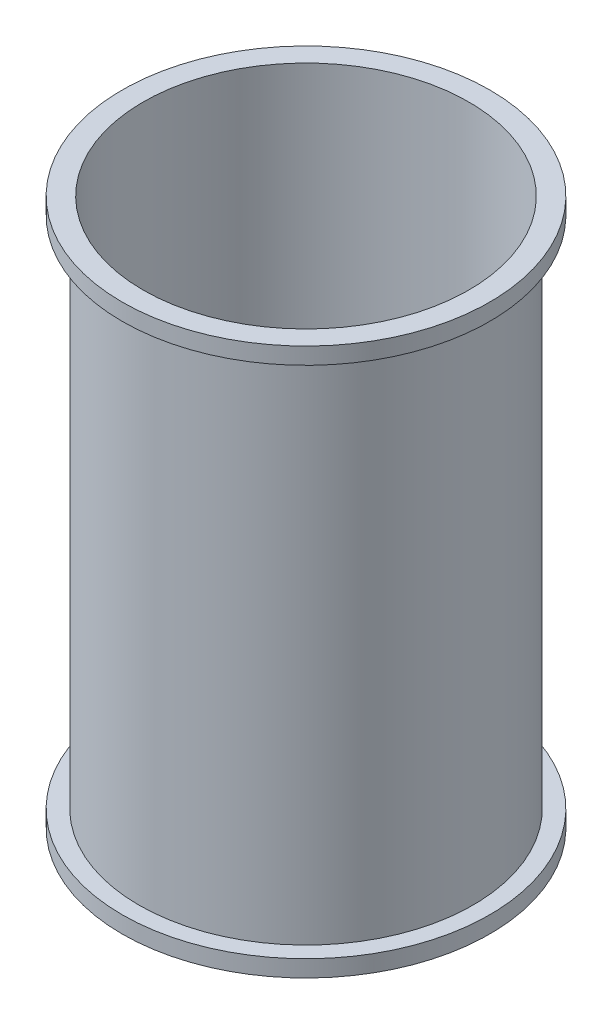
SolidWorks part; units mm, degrees
material "AISI 304"
ref_plane "Front Plane" through (0, 0, 0) normal (0, 0, 1) x (1, 0, 0)
ref_plane "Top Plane" through (0, 0, 0) normal (0, 1, 0) x (1, 0, 0)
ref_plane "Right Plane" through (0, 0, 0) normal (1, 0, 0) x (0, 0, -1)
sketch "Sketch1" plane through (0, 0, 0) normal (0, 1, 0) x (1, 0, 0)
  circle A0 centre (0, 0) radius 123.825
  circle A1 centre (0, 0) radius 139.7
  circle A2 centre (0, 0) radius 127
  dimension "D1" = 279.4
  dimension "D2" = 247.65
  dimension "D3" = 254
extrude "Boss-Extrude1" add sketch "Sketch1" along normal blind 416.052 contours A2 A0 region at (-126.6408, 0, 0)
extrude "Boss-Extrude2" add sketch "Sketch1<3>" along normal blind 12.7 contours A1 A2 region at (-135.7487, 0, 0)
sketch "Sketch1<3>" plane through (0, 0, 0) normal (0, 1, 0) x (1, 0, 0) same geometry as "Sketch1"
extrude "Boss-Extrude4" add sketch "Sketch1<5>" along normal blind 12.7 from offset 403.352 contours A1 A2 region at (-135.7487, 0, 0)
sketch "Sketch1<5>" plane through (0, 0, 0) normal (0, 1, 0) x (1, 0, 0) same geometry as "Sketch1"
